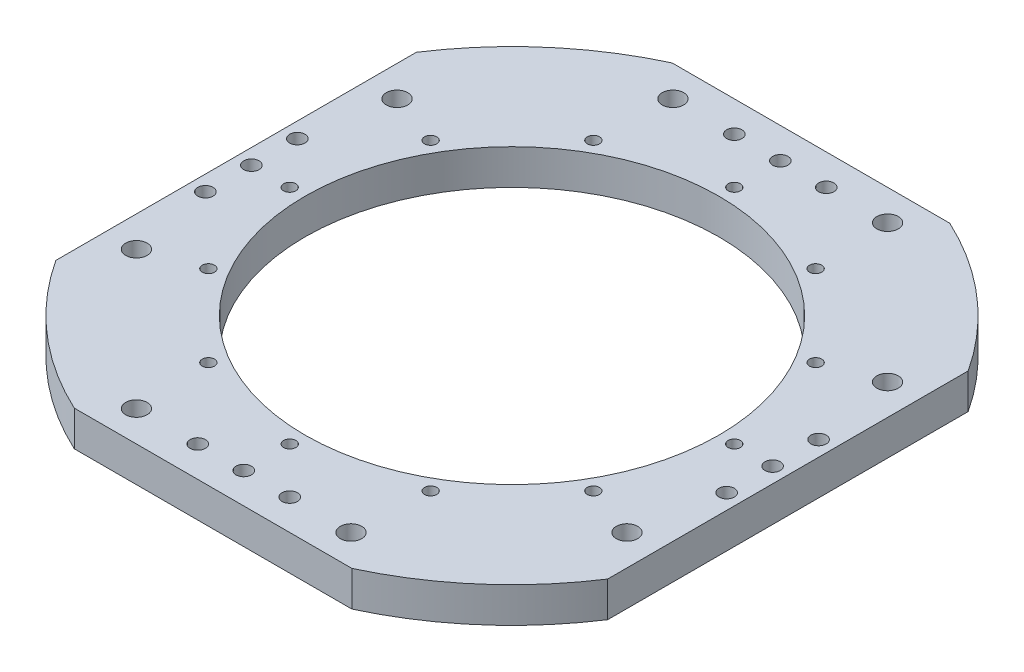
SolidWorks part; units mm, degrees
ref_plane "前视基准面" through (0, 0, 0) normal (0, 0, 1) x (1, 0, 0)
ref_plane "上视基准面" through (0, 0, 0) normal (0, 1, 0) x (1, 0, 0)
ref_plane "右视基准面" through (0, 0, 0) normal (1, 0, 0) x (0, 0, -1)
other "Configuration Table"
sketch "草图1" plane through (0, 0, 0) normal (0, 1, 0) x (1, 0, 0)
  line L0 (-180, 117.5798) -> (-180, -117.5798)
  line L1 (-180, 195) -> (180, 195) construction
  line L2 (-180, 195) -> (-180, -195) construction
  line L3 (-180, -195) -> (180, -195) construction
  line L4 (180, 195) -> (180, -195) construction
  line L5 (-180, 195) -> (180, -195) construction
  line L6 (-180, -195) -> (180, 195) construction
  line L7 (-90.5539, -195) -> (90.5539, -195)
  line L8 (180, -117.5798) -> (180, 117.5798)
  line L9 (-90.5539, 195) -> (90.5539, 195)
  arc A0 (90.5539, -195) -> (180, -117.5798) centre (0, 0) ccw
  arc A1 (-180, -117.5798) -> (-90.5539, -195) centre (0, 0) ccw
  arc A2 (-90.5539, 195) -> (-180, 117.5798) centre (0, 0) ccw
  arc A3 (180, 117.5798) -> (90.5539, 195) centre (0, 0) ccw
  circle A4 centre (0, 0) radius 135
  circle A5 centre (0, 0) radius 145 construction
  circle A6 centre (0, 145) radius 4
  circle A7 centre (72.5, 125.5737) radius 4
  circle A8 centre (125.5737, 72.5) radius 4
  circle A9 centre (145, 0) radius 4
  circle A10 centre (125.5737, -72.5) radius 4
  circle A11 centre (72.5, -125.5737) radius 4
  circle A12 centre (0, -145) radius 4
  circle A13 centre (-72.5, -125.5737) radius 4
  circle A14 centre (-125.5737, -72.5) radius 4
  circle A15 centre (-145, 0) radius 4
  circle A16 centre (-125.5737, 72.5) radius 4
  circle A17 centre (-72.5, 125.5737) radius 4
  point P18 (98.2928, 65.9525)
  point P19 (0, 0)
  point P42 (0, 0)
  dimension "D1" = 430
  dimension "D4" = 270
  dimension "D5" = 290
  dimension "D6" = 8
  dimension "D2" = 390
  dimension "D3" = 360
  dimension "D7" = 12
extrude "凸台-拉伸1" add sketch "草图1" along normal mid plane 23
sketch "草图2" plane through (0, 11.5, 0) normal (0, 1, 0) x (1, 0, 0)
  line L0 (0, 195) -> (0, 0) construction
  line L1 (90.5539, 195) -> (-90.5539, 195) construction
  line L2 (0, 0) -> (180, 0) construction
  line L3 (180, -117.5798) -> (180, 117.5798) construction
  circle A0 centre (0, 175) radius 5
  circle A1 centre (-30, 175) radius 5
  circle A2 centre (-70, 175) radius 7
  circle A3 centre (70, 175) radius 7
  circle A4 centre (30, 175) radius 5
  circle A5 centre (-70, -175) radius 7
  circle A6 centre (-30, -175) radius 5
  circle A7 centre (0, -175) radius 5
  circle A8 centre (30, -175) radius 5
  circle A9 centre (70, -175) radius 7
  circle A10 centre (160, 85) radius 7
  circle A11 centre (170, 30) radius 5
  circle A12 centre (170, 0) radius 5
  circle A13 centre (160, -85) radius 7
  circle A14 centre (170, -30) radius 5
  circle A15 centre (-170, -30) radius 5
  circle A16 centre (-160, -85) radius 7
  circle A17 centre (-170, 0) radius 5
  circle A18 centre (-170, 30) radius 5
  circle A19 centre (-160, 85) radius 7
  point P34 (0, 0)
  point P35 (156.2756, 85)
  point P40 (157.5904, -85)
  dimension "D1" = 10
  dimension "D4" = 10
  dimension "D6" = 14
  dimension "D2" = 350
  dimension "D3" = 60
  dimension "D5" = 140
  dimension "D7" = 340
  dimension "D8" = 170
  dimension "D9" = 60
  dimension "D10" = 20
extrude "切除-拉伸1" cut sketch "草图2" against normal blind 23
